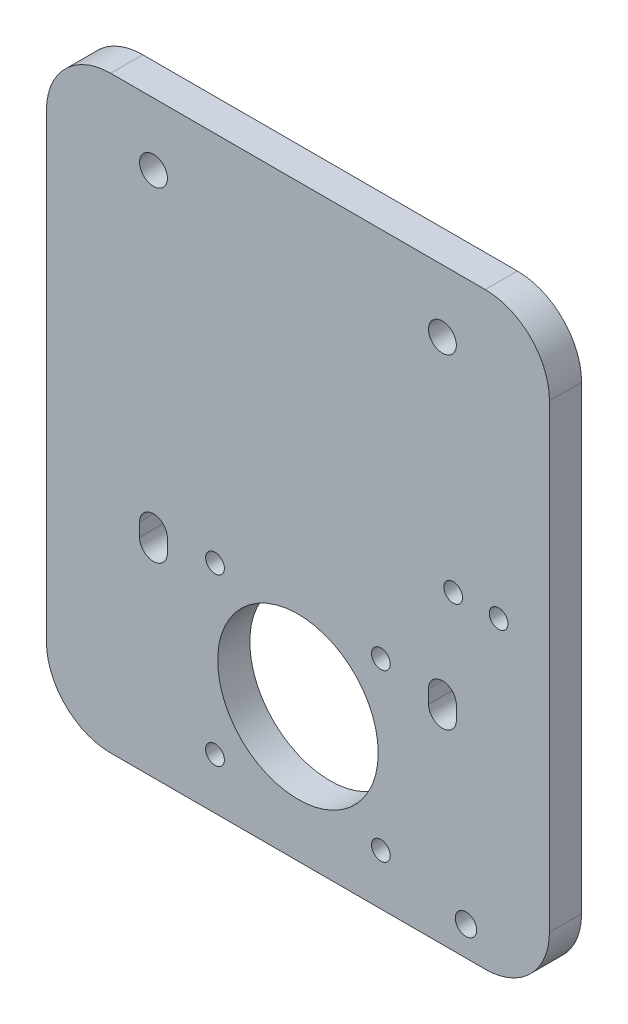
SolidWorks part; units mm, degrees
material "Acrylic (Medium-high impact)"
ref_plane "Спереди" through (0, 0, 0) normal (0, 0, 1) x (1, 0, 0)
ref_plane "Сверху" through (0, 0, 0) normal (0, 1, 0) x (1, 0, 0)
ref_plane "Справа" through (0, 0, 0) normal (1, 0, 0) x (0, 0, -1)
sketch "Model" plane through (0, 0, 0) normal (0, 0, 1) x (1, 0, 0)
  line L4 (-22.7195, 98.3) -> (-31.6357, 98.3) construction
  line L5 (-27, 102.2644) -> (-27, 93.0751) construction
  line L24 (-27, 44.8397) -> (-27, 32.6753) construction
  line L25 (-29.6, 40.1) -> (-29.6, 37.6)
  line L26 (-24.4, 37.6) -> (-24.4, 40.1)
  line L27 (-24.4, 40.1) -> (-24.4, 37.6)
  line L28 (-29.6, 37.6) -> (-29.6, 40.1)
  line L156 (-18.8648, 25) -> (20.0371, 25) construction
  line L157 (13.2088, 9.5) -> (17.9881, 9.5) construction
  line L158 (15.5, 11.4003) -> (15.5, 7.7373) construction
  line L159 (27, 44.8397) -> (27, 32.6753) construction
  line L160 (47, 98) -> (47, 12)
  line L165 (27, 102.2644) -> (27, 93.0751) construction
  line L166 (22.7195, 98.3) -> (31.6357, 98.3) construction
  line L167 (35, 0) -> (-35, 0)
  line L171 (15.5, 38.5997) -> (15.5, 42.2627) construction
  line L172 (13.2088, 40.5) -> (17.9881, 40.5) construction
  line L173 (-13.2088, 40.5) -> (-17.9881, 40.5) construction
  line L174 (-47, 12) -> (-47, 98)
  line L175 (-15.5, 38.5997) -> (-15.5, 42.2627) construction
  line L176 (-15.5, 11.4003) -> (-15.5, 7.7373) construction
  line L177 (-13.2088, 9.5) -> (-17.9881, 9.5) construction
  line L181 (-35, 110) -> (35, 110)
  line L955 (29.6, 37.6) -> (29.6, 40.1)
  line L968 (24.4, 40.1) -> (24.4, 37.6)
  line L1360 (24.4, 37.6) -> (24.4, 40.1)
  line L1373 (29.6, 40.1) -> (29.6, 37.6)
  line L1604 (0, -6.1891) -> (0, 116.9068) construction
  arc A0 (35, 110) -> (47, 98) centre (35, 98) cw
  arc A1 (47, 12) -> (35, 0) centre (35, 12) cw
  arc A2 (-47, 12) -> (-35, 0) centre (-35, 12) ccw
  arc A3 (-47, 98) -> (-35, 110) centre (-35, 98) cw
  circle A4 centre (15.5, 9.5) radius 1.75
  circle A5 centre (15.5, 40.5) radius 1.75
  circle A6 centre (-15.5, 40.5) radius 1.75
  circle A7 centre (-15.5, 9.5) radius 1.75
  circle A8 centre (0, 25) radius 15
  arc A9 (24.4, 40.1) -> (29.6, 40.1) centre (27, 40.1) cw
  arc A10 (24.4, 37.6) -> (29.6, 37.6) centre (27, 37.6) ccw
  circle A19 centre (27, 98.3) radius 2.6
  circle A22 centre (-27, 98.3) radius 2.6
  arc A29 (-24.4, 37.6) -> (-29.6, 37.6) centre (-27, 37.6) cw
  arc A30 (-24.4, 40.1) -> (-29.6, 40.1) centre (-27, 40.1) ccw
  dimension "D1" = 12
  dimension "D11" = 3.5
  dimension "D12" = 30
  dimension "D15" = 2.6
  dimension "D16" = 2.6
  dimension "D38" = 5.2
  dimension "D2" = 70
  dimension "D3" = 110
  dimension "D4" = 25
  dimension "D5" = 15.5
  dimension "D6" = 15.5
  dimension "D7" = 20
  dimension "D13" = 5.2
  dimension "D14" = 2.5
  dimension "D17" = 12.6
  dimension "D36" = 58.2
  dimension "D37" = 27
extrude "Base" add sketch "Model" along normal blind 6 contours A3 L174 A2 L167 A1 L160 A0 L181 A30 L26 A29 L25 A7 A6 A4 A5 A8 A10 L968 A9 L955 region at (0, 57.3106, 0)
sketch "Sketch1" plane through (0, 0, 0) normal (0, 0, -1) x (-1, 0, 0)
  line L1 (-35, 0) -> (35, 0) construction
  line L3 (-47, 98) -> (-47, 12) construction
  circle A0 centre (-29, 58) radius 1.75
  circle A1 centre (-37.5, 58) radius 1.75
  dimension "D1" = 3.5
  dimension "D3" = 9.5
  dimension "D4" = 8.5
  dimension "D5" = 58
extrude "CableMount" cut sketch "Sketch1" against normal blind 10
sketch "Sketch2" plane through (0, 0, 6) normal (0, 0, 1) x (1, 0, 0)
  circle A0 centre (31.3948, 5.5057) radius 2
  dimension "D1" = 4
extrude "Cut-Extrude1" cut sketch "Sketch2" against normal through all
